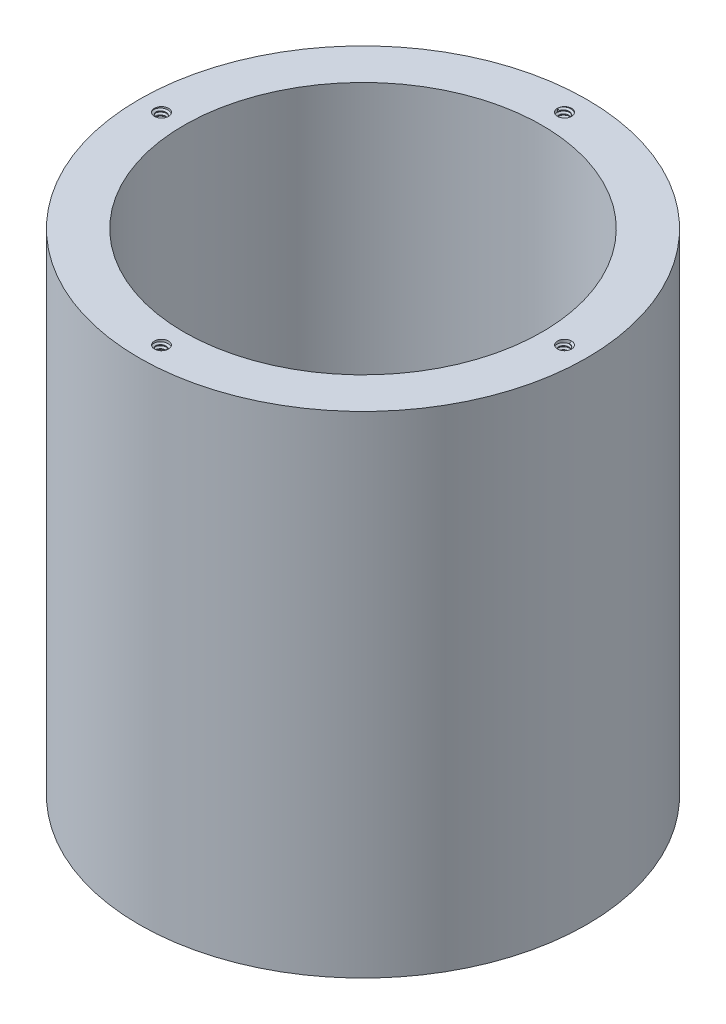
SolidWorks part; units mm, degrees
material "1060 Alloy"
ref_plane "Front Plane" through (0, 0, 0) normal (0, 0, 1) x (1, 0, 0)
ref_plane "Top Plane" through (0, 0, 0) normal (0, 1, 0) x (1, 0, 0)
ref_plane "Right Plane" through (0, 0, 0) normal (1, 0, 0) x (0, 0, -1)
sketch "Sketch1" plane through (0, 0, 0) normal (0, 1, 0) x (1, 0, 0)
  circle A0 centre (0, 0) radius 15.875
  circle A1 centre (0, 0) radius 12.7
  dimension "D1" = 31.75
  dimension "D2" = 25.4
extrude "Boss-Extrude1" add sketch "Sketch1" along normal blind 34.8
sketch "Sketch2" plane through (0, 34.8, 0) normal (0, 1, 0) x (1, 0, 0)
  circle A0 centre (0, 14.29) radius 0.5
  circle A2 centre (0, 0) radius 12.7 construction
  dimension "D1" = 1
  dimension "D2" = 14.29
extrude "Cut-Extrude1" cut sketch "Sketch2" against normal blind 2
thread "Thread1" pitch 0.25 method extrude profile "Thread Profile1" start angle 0, offset 0, length 2, pitch 0.25, diameter 1
ref_plane "Plane1" through (-0.5, 34.8, -14.29) normal (0, 0, 1) x (-1, 0, 0)
sketch "Thread Profile1" plane through (-0.5, 34.8, -14.29) normal (0, 0, 1) x (-1, 0, 0)
  line L0 (0, 0) -> (0, 0.25) construction
  line L11 (0, 0) -> (0, 0.2187)
  line L12 (0, 0.2187) -> (-0.1353, 0.1406)
  line L13 (-0.1353, 0.1406) -> (-0.1353, 0.0781)
  line L15 (-0.1353, 0.0781) -> (0, 0)
  line L17 (-0.1353, 0.1094) -> (0, 0.1094) construction
  point P2 (0, 0)
  dimension "Pitch" = 0.25
  dimension "Profile_Angle" = 60
  dimension "Profile_Land" = 0.0625
  dimension "Profile_Height" = 0.1353
pattern_circular "CirPattern1" count 4 over 360 about axis through (0, 34.8, 0) along (0, 1, 0) of "Cut-Extrude1", "Thread1"
sketch "Sketch5" plane through (0, 0, 0) normal (0, -1, 0) x (1, 0, 0)
  circle A0 centre (0, 14.29) radius 0.5
  dimension "D1" = 1
  dimension "D2" = 14.29
extrude "Cut-Extrude2" cut sketch "Sketch5" against normal blind 2
thread "Thread2" pitch 0.25 method extrude profile "Thread Profile2" start angle 0, offset 0, length 2, pitch 0.25, diameter 1
ref_plane "Plane2" through (0.5, 0, 14.29) normal (0, 0, 1) x (1, 0, 0)
sketch "Thread Profile2" plane through (0.5, 0, 14.29) normal (0, 0, 1) x (1, 0, 0)
  line L0 (0, 0) -> (0, 0.25) construction
  line L11 (0, 0) -> (0, 0.2187)
  line L12 (0, 0.2187) -> (-0.1353, 0.1406)
  line L13 (-0.1353, 0.1406) -> (-0.1353, 0.0781)
  line L15 (-0.1353, 0.0781) -> (0, 0)
  line L17 (-0.1353, 0.1094) -> (0, 0.1094) construction
  point P2 (0, 0)
  dimension "Pitch" = 0.25
  dimension "Profile_Angle" = 60
  dimension "Profile_Land" = 0.0625
  dimension "Profile_Height" = 0.1353
pattern_circular "CirPattern2" count 4 over 360 about axis through (0, 0, 0) along (0, 1, 0) of "Cut-Extrude2", "Thread2"
